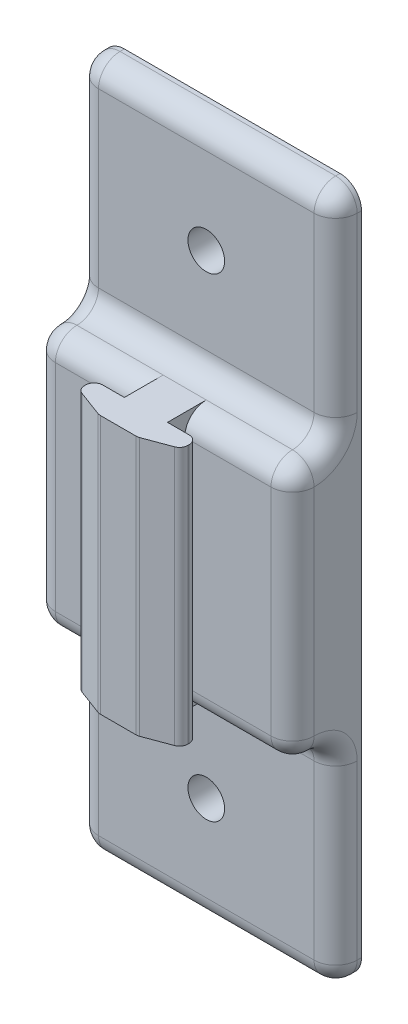
SolidWorks part; units mm, degrees
ref_plane "Plan de face" through (0, 0, 0) normal (0, 0, 1) x (1, 0, 0)
ref_plane "Plan de dessus" through (0, 0, 0) normal (0, 1, 0) x (1, 0, 0)
ref_plane "Plan de droite" through (0, 0, 0) normal (1, 0, 0) x (0, 0, -1)
sketch "Esquisse1" plane through (0, 0, 0) normal (0, 0, 1) x (1, 0, 0)
  line L1 (0, 0) -> (30, 0)
  line L2 (0, 0) -> (0, 80)
  line L3 (0, 80) -> (30, 80)
  line L4 (30, 0) -> (30, 80)
  dimension "D1" = 80
  dimension "D2" = 30
extrude "Boss.-Extru.1" add sketch "Esquisse1" along normal blind 3
sketch "Esquisse2" plane through (0, 0, 3) normal (0, 0, 1) x (1, 0, 0)
  line L0 (0, 0) -> (30, 0) construction
  circle A0 centre (15, 67.5) radius 2.125
  circle A1 centre (15, 12.5) radius 2.125
  dimension "D1" = 4.25
  dimension "D2" = 55
  dimension "D3" = 12.5
extrude "Enlèv. mat.-Extru.1" cut sketch "Esquisse2" against normal blind 3
sketch "Esquisse3" plane through (0, 0, 3) normal (0, 0, 1) x (1, 0, 0)
  line L0 (0, 80) -> (0, 0) construction
  line L1 (0, 55) -> (30, 55)
  line L2 (0, 55) -> (0, 25)
  line L3 (0, 25) -> (30, 25)
  line L4 (30, 55) -> (30, 25)
  line L5 (30, 80) -> (0, 80) construction
  line L6 (0, 0) -> (30, 0) construction
  point P10 (-5, 25)
  dimension "D1" = 30
  dimension "D2" = 0
  dimension "D3" = 25
  dimension "D4" = 25
extrude "Boss.-Extru.2" add sketch "Esquisse3" along normal blind 5
sketch "Esquisse4" plane through (0, 25, 0) normal (0, -1, 0) x (-1, 0, 0)
  line L0 (-12.5, -8) -> (-12.5, -10)
  line L1 (0, -8) -> (-30, -8) construction
  line L2 (-12.5, -10) -> (-9, -10)
  line L3 (-9, -10) -> (-9, -11.81)
  line L4 (-9, -11.81) -> (-12.75, -13.2019)
  line L5 (-12.75, -13.2019) -> (-17.25, -13.2019)
  line L6 (-17.25, -13.2019) -> (-21, -11.81)
  line L7 (-21, -11.81) -> (-21, -10)
  line L8 (-21, -10) -> (-17.5, -10)
  line L9 (-17.5, -10) -> (-17.5, -8)
  line L10 (-17.5, -8) -> (-12.5, -8)
  dimension "D1" = 4.5
  dimension "D2" = 3.5
  dimension "D3" = 3.5
  dimension "D4" = 5
  dimension "D5" = 4
  dimension "D6" = 4
  dimension "D7" = 1.81
  dimension "D8" = 1.81
  dimension "D9" = 2
  dimension "D10" = 2
  dimension "D11" = 12.5
extrude "Boss.-Extru.3" add sketch "Esquisse4" against normal up to surface (30 mm away) up to face at (15, 55, 5.5)
fillet "Congé1" radius 1 6 edges at (9, 40, 10) (9, 40, 11.81) (12.75, 40, 13.2019) (17.25, 40, 13.2019) (21, 40, 11.81) (21, 40, 10)
fillet "Congé2" radius 2.5 18 edges at (0, 0, 1.5) (30, 40, 8) (0, 40, 8) (30, 80, 1.5) (0, 80, 1.5) (15, 80, 3) (15, 55, 3) (30, 67.5, 3) (0, 67.5, 3) (30, 0, 1.5) (15, 0, 3) (0, 12.5, 3) (30, 12.5, 3) (23.75, 25, 8) (15, 25, 3) (6.25, 25, 8) (23.75, 55, 8) (6.25, 55, 8)
